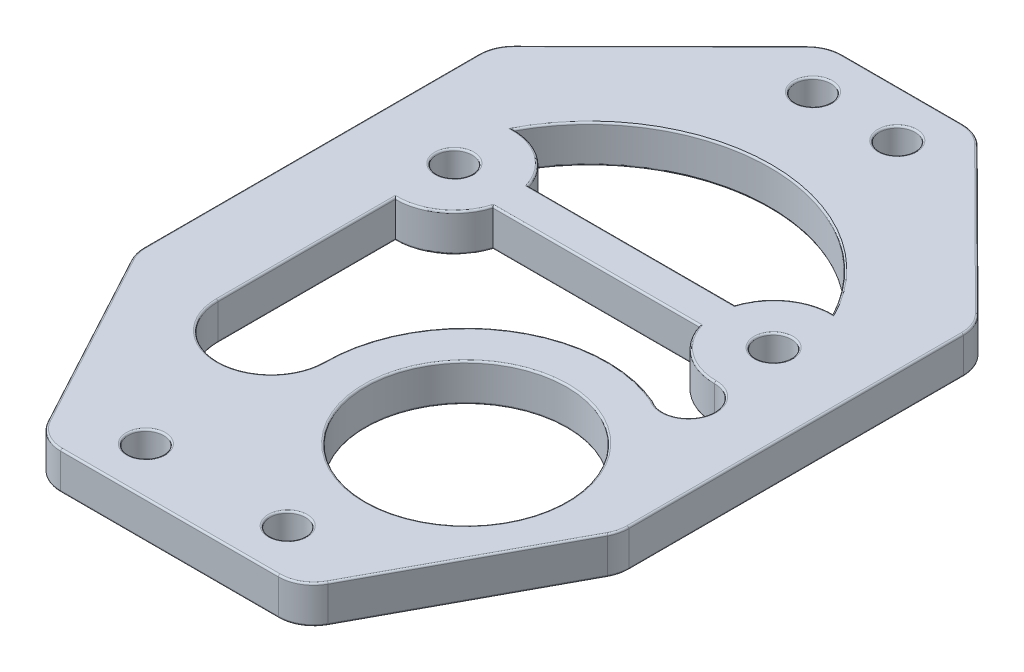
SolidWorks part; units mm, degrees
ref_plane "Front Plane" through (0, 0, 0) normal (0, 0, 1) x (1, 0, 0)
ref_plane "Top Plane" through (0, 0, 0) normal (0, 1, 0) x (1, 0, 0)
ref_plane "Right Plane" through (0, 0, 0) normal (1, 0, 0) x (0, 0, -1)
sketch "Sketch1" plane through (0, 0, 0) normal (0, 1, 0) x (1, 0, 0)
  line L0 (0, 0) -> (0, 62) construction
  line L1 (0, 0) -> (-11, 0)
  line L2 (-11, 0) -> (-20.5, 17.5997)
  line L3 (-20.5, 17.5997) -> (-20.5, 47.8997)
  line L4 (-20.5, 47.8997) -> (-6.3161, 62)
  line L5 (-6.3161, 62) -> (6.3161, 62)
  line L6 (11, 0) -> (20.5, 17.5997)
  line L7 (20.5, 17.5997) -> (20.5, 47.8997)
  line L8 (20.5, 47.8997) -> (6.3161, 62)
  line L9 (7.5, 17.5997) -> (20.5, 17.5997) construction
  line L10 (13.5, 37.5997) -> (-13.5, 37.5997) construction
  line L11 (-8.7303, 36.0997) -> (8.7303, 36.0997)
  line L12 (8.7303, 39.0997) -> (-8.7303, 39.0997) construction
  line L13 (8.7303, 39.0997) -> (8.7303, 36.0997) construction
  line L14 (8.7303, 36.0997) -> (-8.7303, 36.0997) construction
  line L15 (-8.7303, 39.0997) -> (-8.7303, 36.0997) construction
  line L16 (8.7303, 39.0997) -> (-8.7303, 36.0997) construction
  line L17 (8.7303, 36.0997) -> (-8.7303, 39.0997) construction
  line L18 (13.5, 37.5997) -> (12.2337, 28.6266) construction
  line L19 (-13.5, 37.5997) -> (-13.5, 17.5997)
  line L20 (0, 0) -> (11, 0)
  line L21 (8.7303, 39.0997) -> (-8.7303, 39.0997)
  circle A0 centre (-3.5661, 58) radius 1.5
  circle A2 centre (-6, 4) radius 1.5
  circle A3 centre (-13.5, 37.5997) radius 1.5
  circle A4 centre (6, 4) radius 1.5
  circle A5 centre (13.5, 37.5997) radius 1.5
  circle A6 centre (3.5661, 58) radius 1.5
  circle A7 centre (7.5, 17.5997) radius 8.5
  circle A8 centre (13.5, 37.5997) radius 5 construction
  circle A9 centre (-13.5, 37.5997) radius 5 construction
  circle A10 centre (7.5, 17.5997) radius 12 construction
  arc A11 (-13.5, 42.5997) -> (13.5, 42.5997) centre (0, 35.5343) cw
  arc A12 (13.5, 42.5997) -> (8.7303, 39.0997) centre (13.5, 37.5997) ccw
  arc A13 (-13.5, 42.5997) -> (-8.7303, 39.0997) centre (-13.5, 37.5997) cw
  arc A14 (-8.7303, 36.0997) -> (-13.5, 32.5997) centre (-13.5, 37.5997) cw
  arc A15 (8.7303, 36.0997) -> (13.5, 32.5997) centre (13.5, 37.5997) ccw
  arc A16 (13.5, 32.5997) -> (12.2337, 28.6266) centre (13.5, 30.4114) cw
  arc A17 (12.2337, 28.6266) -> (-4.5, 17.5997) centre (7.5, 17.5997) ccw
  arc A18 (-13.5, 17.5997) -> (-4.5, 17.5997) centre (-9, 17.5997) ccw
  arc A19 (8.7303, 39.0997) -> (8.7303, 36.0997) centre (13.5, 37.5997) ccw
  arc A20 (-8.7303, 39.0997) -> (-8.7303, 36.0997) centre (-13.5, 37.5997) cw
  point P35 (0, 37.5997)
  dimension "D2" = 10.3
  dimension "D3" = 3
  dimension "D4" = 3
  dimension "D5" = 6
  dimension "D11" = 4
  dimension "D12" = 4
  dimension "D15" = 3
  dimension "D16" = 17
  dimension "D23" = 3
  dimension "D1" = 62
  dimension "D6" = 11
  dimension "D7" = 20
  dimension "D8" = 30.3
  dimension "D9" = 20
  dimension "D10" = 20.5
  dimension "D13" = 2.75
  dimension "D14" = 7
  dimension "D17" = 13
  dimension "D22" = 3
  dimension "D18" = 3.5
  dimension "D19" = 3.5
  dimension "D20" = 3.5
extrude "Boss-Extrude2" add sketch "Sketch1" along normal blind 3.18 contours L1 L20 L6 L7 L8 L5 L4 L3 L2 A20 A13 A11 A12 A19 A15 A16 A17 A18 L19 A3 A14 A7 A5 A0 A2 A4 A6 | L21 A20 L11 A19 region at (-5.5, 0, -0.7433) region at (0, 0, -37.5997)
fillet "Fillet1" radius 3 8 edges at (-6.3161, 1.59, -62) (6.3161, 1.59, -62) (20.5, 1.59, -47.8997) (20.5, 1.59, -17.5997) (11, 1.59, 0) (-11, 1.59, 0) (-20.5, 1.59, -17.5997) (-20.5, 1.59, -47.8997)
fillet "Fillet3" radius 0.15 68 edges at (3.5661, 3.18, -56.5) (6, 3.18, -2.5) (-6, 3.18, -2.5) (-3.5661, 3.18, -56.5) (6.2226, 3.18, -61.7733) (13.4044, 3.18, -54.9535) (20.2699, 3.18, -47.804) (20.5, 3.18, -32.5048) (20.4086, 3.18, -17.6228) (15.9951, 3.18, -9.2539) (10.7472, 3.18, -0.4237) (0, 3.18, 0) (-10.7472, 3.18, -0.4237) (-15.9951, 3.18, -9.2539) (-20.4086, 3.18, -17.6228) (-20.5, 3.18, -32.5048) (-20.2699, 3.18, -47.804) (-13.4044, 3.18, -54.9535) (-6.2226, 3.18, -61.7733) (0, 3.18, -62) (13.5, 3.18, -36.0997) (7.5, 3.18, -9.0997) (-13.5, 3.18, -36.0997) (10.542, 3.18, -41.6308) (0, 3.18, -50.7714) (-10.542, 3.18, -41.6308) (0, 3.18, -39.0997) (-13.5, 3.18, -25.0997) (-9, 3.18, -13.0997) (0.8972, 3.18, -27.6198) (15.585, 3.18, -29.7469) (10.542, 3.18, -33.5686) (0, 3.18, -36.0997) (-10.542, 3.18, -33.5686) (3.5661, 0, -56.5) (6, 0, -2.5) (-6, 0, -2.5) (-3.5661, 0, -56.5) (-20.2699, 0, -47.804) (-20.5, 0, -32.5048) (-20.4086, 0, -17.6228) (-15.9951, 0, -9.2539) (-10.7472, 0, -0.4237) (0, 0, 0) (10.7472, 0, -0.4237) (15.9951, 0, -9.2539) (20.4086, 0, -17.6228) (20.5, 0, -32.5048) (20.2699, 0, -47.804) (13.4044, 0, -54.9535) (6.2226, 0, -61.7733) (0, 0, -62) (-6.2226, 0, -61.7733) (-13.4044, 0, -54.9535) (13.5, 0, -36.0997) (7.5, 0, -9.0997) (-13.5, 0, -36.0997) (-10.542, 0, -41.6308) (0, 0, -50.7714) (10.542, 0, -41.6308) (0, 0, -39.0997) (0, 0, -36.0997) (10.542, 0, -33.5686) (15.585, 0, -29.7469) (0.8972, 0, -27.6198) (-9, 0, -13.0997) (-13.5, 0, -25.0997) (-10.542, 0, -33.5686)
